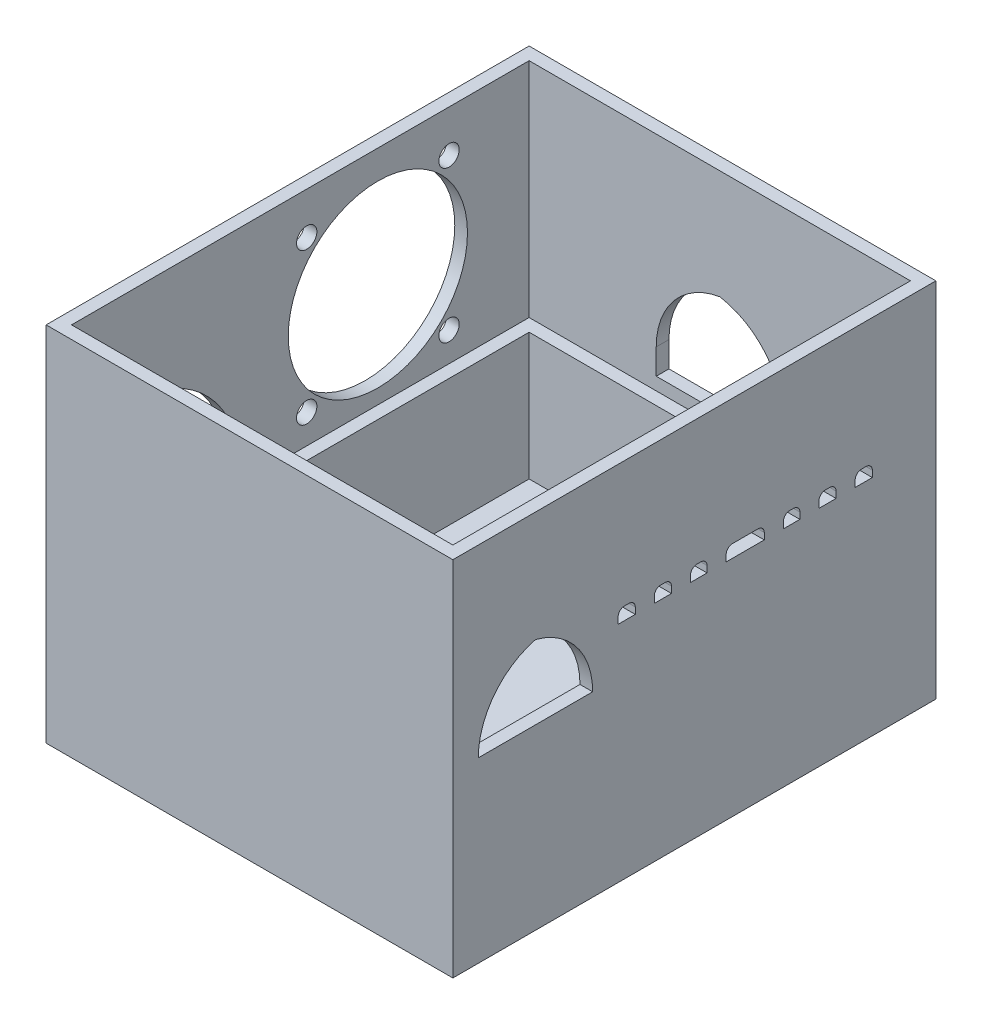
SolidWorks part; units mm, degrees
ref_plane "Front Plane" through (0, 0, 0) normal (0, 0, 1) x (1, 0, 0)
ref_plane "Top Plane" through (0, 0, 0) normal (0, 1, 0) x (1, 0, 0)
ref_plane "Right Plane" through (0, 0, 0) normal (1, 0, 0) x (0, 0, -1)
sketch "Sketch1" plane through (0, 0, 0) normal (0, 1, 0) x (1, 0, 0)
  line L1 (-32, 38) -> (32, 38)
  line L2 (-32, 38) -> (-32, -38)
  line L3 (-32, -38) -> (32, -38)
  line L4 (32, 38) -> (32, -38)
  line L5 (-32, 38) -> (32, -38) construction
  line L6 (-32, -38) -> (32, 38) construction
  point P0 (0, 0)
  dimension "D1" = 64
  dimension "D2" = 76
extrude "Base" add sketch "Sketch1" along normal blind 57
sketch "Sketch3" plane through (0, 57, 0) normal (0, 1, 0) x (1, 0, 0)
  line L0 (-32, 38) -> (-32, -38) construction
  line L1 (-30, 36) -> (30, 36)
  line L2 (-30, 36) -> (-30, -36)
  line L3 (-30, -36) -> (30, -36)
  line L4 (30, 36) -> (30, -36)
  line L5 (-30, 36) -> (30, -36) construction
  line L6 (-30, -36) -> (30, 36) construction
  line L7 (32, 38) -> (-32, 38) construction
  point P0 (0, 0)
  dimension "D1" = 2
  dimension "D2" = 2
  dimension "D3" = 72
  dimension "D4" = 60
extrude "Top Layer" cut sketch "Sketch3" against normal blind 35
sketch "Sketch4" plane through (0, 22, 0) normal (0, 1, 0) x (1, 0, 0)
  line L1 (-28, 34) -> (28, 34)
  line L2 (-28, 34) -> (-28, -34)
  line L3 (-28, -34) -> (28, -34)
  line L4 (28, 34) -> (28, -34)
  line L5 (-28, 34) -> (28, -34) construction
  line L6 (-28, -34) -> (28, 34) construction
  point P0 (0, 0)
  dimension "D1" = 68
  dimension "D2" = 56
extrude "Bottom Layer Battery" cut sketch "Sketch4" against normal blind 20
sketch "Sketch5" plane through (-30, 0, 0) normal (1, 0, 0) x (0, 0, -1)
  line L0 (12.2, 24.3) -> (-10.6327, 24.3) construction
  line L1 (12.2, 24.3) -> (12.2, 52.5) construction
  line L2 (36, 22) -> (-36, 22) construction
  line L3 (-1.9, 38.4) -> (26.3, 38.4) construction
  line L4 (1, 25) -> (2.9017, 25) construction
  line L5 (1, 50.4) -> (1, 57) construction
  line L6 (36, 57) -> (-36, 57) construction
  line L8 (23.4, 50.4) -> (23.4, 57) construction
  circle A0 centre (12.2, 38.4) radius 14.1
  circle A1 centre (1, 26.6) radius 1.6
  circle A2 centre (23.4, 26.6) radius 1.6
  circle A5 centre (1, 50.4) radius 1.6
  circle A6 centre (23.4, 50.4) radius 1.6
  dimension "D1" = 28.2
  dimension "D2" = 2.3
  dimension "D6" = 3.2
  dimension "D3" = 3
  dimension "D4" = 3.2
  dimension "D5" = 3.2
extrude "Fan Hole" cut sketch "Sketch5" against normal blind 2
sketch "Sketch6" plane through (30, 0, 0) normal (-1, 0, 0) x (0, 0, 1)
  line L0 (36, 22) -> (-36, 22) construction
  line L1 (34, 28) -> (16, 28)
  line L2 (34, 28) -> (34, 40)
  line L3 (34, 40) -> (16, 40)
  line L4 (16, 28) -> (16, 40)
  line L7 (36, 22) -> (36, 57) construction
  dimension "D1" = 2
  dimension "D2" = 18
  dimension "D3" = 6
  dimension "D4" = 12
extrude "SD Hole" cut sketch "Sketch6" against normal blind 2
fillet "SD fillet" radius 12 2 edges at (31, 40, 16) (31, 40, 34)
sketch "Sketch12" plane through (-30, 0, 0) normal (1, 0, 0) x (0, 0, -1)
  line L0 (36, 22) -> (-36, 22) construction
  line L1 (-33.5, 24) -> (-9.5, 24)
  line L2 (-33.5, 24) -> (-33.5, 42)
  line L3 (-33.5, 42) -> (-9.5, 42)
  line L4 (-9.5, 24) -> (-9.5, 42)
  line L5 (-36, 22) -> (-36, 57) construction
  dimension "D1" = 2
  dimension "D2" = 24
  dimension "D3" = 18
  dimension "D4" = 2.5
extrude "USB-C" cut sketch "Sketch12" against normal blind 2
fillet "USB-C Fillet" radius 18 2 edges at (-31, 42, 33.5) (-31, 42, 9.5)
sketch "Sketch7" plane through (30, 0, 0) normal (-1, 0, 0) x (0, 0, 1)
  line L0 (-36, 22) -> (-36, 57) construction
  line L1 (-28, 37.1966) -> (12, 37.1966)
  line L2 (-28, 37.1966) -> (-28, 35.1966)
  line L3 (-28, 35.1966) -> (12, 35.1966)
  line L4 (12, 37.1966) -> (12, 35.1966)
  dimension "D1" = 2
  dimension "D2" = 40
  dimension "D3" = 8
extrude "Hole in wall" cut sketch "Sketch7" against normal blind 2
sketch "Sketch9" plane through (0, 35.1966, 0) normal (0, 1, 0) x (1, 0, 0)
  line L0 (30, 8) -> (32, 8) construction
  line L1 (30, -9.3) -> (32, -9.3)
  line L2 (30, -9.3) -> (30, -6.3)
  line L3 (30, -6.3) -> (32, -6.3)
  line L4 (32, -9.3) -> (32, -6.3)
  line L5 (30, -3.6) -> (32, -3.6)
  line L6 (30, -3.6) -> (30, -0.6)
  line L7 (30, -0.6) -> (32, -0.6)
  line L8 (32, -3.6) -> (32, -0.6)
  line L13 (30, 28) -> (30, -12) construction
  line L14 (32, 28) -> (32, -12) construction
  line L15 (32, -12) -> (30, -12) construction
  line L16 (30, 11) -> (32, 11)
  line L17 (30, 2) -> (32, 2)
  line L18 (30, 2) -> (30, 5)
  line L19 (30, 5) -> (32, 5)
  line L20 (32, 2) -> (32, 5)
  line L21 (32, 14) -> (32, 11)
  line L22 (30, 14) -> (32, 14)
  line L23 (30, 14) -> (30, 11)
  line L24 (30, 16.6) -> (32, 16.6)
  line L25 (32, 19.6) -> (32, 16.6)
  line L26 (30, 19.6) -> (32, 19.6)
  line L27 (30, 19.6) -> (30, 16.6)
  line L28 (30, 22.3) -> (32, 22.3)
  line L29 (32, 25.3) -> (32, 22.3)
  line L30 (30, 25.3) -> (32, 25.3)
  line L31 (30, 25.3) -> (30, 22.3)
  dimension "D1" = 2.7
  dimension "D2" = 2.7
  dimension "D3" = 2.6
  dimension "D4" = 3
  dimension "D5" = 3
  dimension "D6" = 3
extrude "Boss-Extrude2" add sketch "Sketch9" along normal blind 2
fillet "Fillet2" radius 1 14 edges at (31, 37.1966, 6.3) (31, 37.1966, 12) (31, 37.1966, 9.3) (31, 37.1966, 3.6) (31, 37.1966, -2) (31, 37.1966, -28) (31, 37.1966, -25.3) (31, 37.1966, -19.6) (31, 37.1966, -22.3) (31, 37.1966, -16.6) (31, 37.1966, -14) (31, 37.1966, 0.6) (31, 37.1966, -5) (31, 37.1966, -11)
sketch "Sketch14" plane through (0, 0, -36) normal (0, 0, 1) x (1, 0, 0)
  line L0 (30, 22) -> (-30, 22) construction
  line L1 (-10, 40) -> (10, 40)
  line L2 (-10, 40) -> (-10, 24)
  line L3 (-10, 24) -> (10, 24)
  line L4 (10, 40) -> (10, 24)
  line L5 (0, 40) -> (0, 24) construction
  line L6 (0, 57) -> (0, 22) construction
  line L7 (30, 57) -> (-30, 57) construction
  dimension "D1" = 16
  dimension "D2" = 20
  dimension "D3" = 2
extrude "Power Hole" cut sketch "Sketch14" against normal blind 2
fillet "Power Fillet" radius 12 2 edges at (10, 40, -37) (-10, 40, -37)
sketch "Sketch11" plane through (0, 2, 0) normal (0, 1, 0) x (1, 0, 0)
  text T0 "<b>Battery Cable</b>\r\n<b>Box v3</b>"
extrude "Words" cut sketch "Sketch11" against normal blind 0.6
